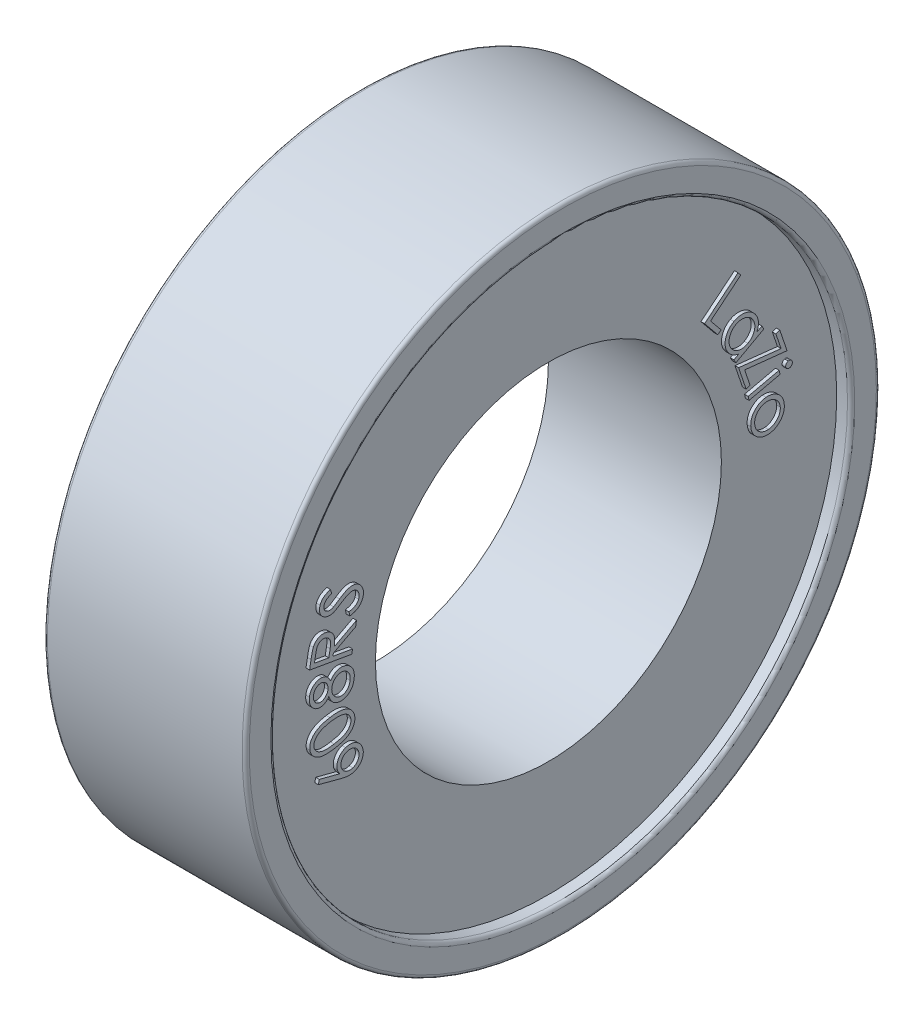
SolidWorks part; units mm, degrees
ref_plane "Front Plane" through (0, 0, 0) normal (0, 0, 1) x (1, 0, 0)
ref_plane "Top Plane" through (0, 0, 0) normal (0, 1, 0) x (1, 0, 0)
ref_plane "Right Plane" through (0, 0, 0) normal (1, 0, 0) x (0, 0, -1)
sketch "Sketch1" plane through (0, 0, 0) normal (1, 0, 0) x (0, 0, -1)
  circle A0 centre (0, 0) radius 6
  circle A1 centre (0, 0) radius 10
  circle A2 centre (0, 0) radius 11
  dimension "D1" = 12
  dimension "D2" = 20
  dimension "D3" = 22
extrude "Boss-Extrude1" add sketch "Sketch1" along normal mid plane 6 contours A1 A0 region at (0, 0, 9.7172)
extrude "Boss-Extrude2" add sketch "Sketch1<3>" along normal mid plane 7 separate body contours A2 A1 region at (0, 0, 10.6889)
sketch "Sketch1<3>" plane through (0, 0, 0) normal (1, 0, 0) x (0, 0, -1) same geometry as "Sketch1"
fillet "Fillet1" radius 0.125 4 edges at (-3.5, 0, -10) (3.5, 0, -10) (3.5, 0, -11) (-3.5, 0, -11)
sketch "Sketch2" plane through (3, 0, 0) normal (1, 0, 0) x (0, 0, -1)
  line L0 (7.8762, 1.8801) -> (7.908, 1.741)
  line L1 (7.908, 1.741) -> (6.8353, 1.4955)
  line L2 (6.8353, 1.4955) -> (6.8035, 1.6347)
  line L3 (6.8035, 1.6347) -> (7.8762, 1.8801)
  line L4 (7.7652, 3.0275) -> (7.9013, 3.0735)
  line L5 (7.9013, 3.0735) -> (8.1528, 2.3304)
  line L6 (8.1528, 2.3304) -> (6.6813, 2.4887)
  line L7 (6.6813, 2.4887) -> (6.8709, 1.9293)
  line L8 (6.8709, 1.9293) -> (6.7339, 1.883)
  line L9 (6.7339, 1.883) -> (6.471, 2.6597)
  line L10 (6.471, 2.6597) -> (7.9446, 2.4978)
  line L11 (7.9446, 2.4978) -> (7.7652, 3.0275)
  line L12 (7.3481, 3.3854) -> (6.3775, 2.8542)
  line L13 (6.3775, 2.8542) -> (6.3102, 2.9771)
  line L14 (6.3102, 2.9771) -> (6.477, 3.0684)
  line L15 (7.1023, 3.4107) -> (7.2808, 3.5083)
  line L16 (7.2808, 3.5083) -> (7.3481, 3.3854)
  line L17 (6.452, 5.5211) -> (6.5472, 5.4045)
  line L18 (6.5472, 5.4045) -> (5.4991, 4.5463)
  line L19 (5.4991, 4.5463) -> (5.8642, 4.1004)
  line L20 (5.8642, 4.1004) -> (5.7522, 4.0088)
  line L21 (5.7522, 4.0088) -> (5.2918, 4.5713)
  line L22 (5.2918, 4.5713) -> (6.452, 5.5211)
  circle A0 centre (0, 0) radius 7 construction
  spline S0 degree 3 poles (8.0554, 0.7678) (8.0592, 0.7269) (8.0581, 0.666) (8.0455, 0.587) (8.0292, 0.531) (8.0076, 0.4772) (7.9701, 0.4074) (7.9327, 0.3603) (7.9054, 0.3306) knots 0 0 0 0 0.258157 0.381467 0.502764 0.62379 0.746181 1 1 1 1
  spline S1 degree 3 poles (7.9054, 0.3306) (7.88, 0.3039) (7.8391, 0.2669) (7.7785, 0.2263) (7.7313, 0.2006) (7.6816, 0.1798) (7.6116, 0.1579) (7.5566, 0.1486) (7.5193, 0.1458) knots 0 0 0 0 0.252774 0.375817 0.498234 0.620232 0.743845 1 1 1 1
  spline S2 degree 3 poles (7.5193, 0.1458) (7.4817, 0.1427) (7.4255, 0.143) (7.3521, 0.1538) (7.2991, 0.1677) (7.2471, 0.1858) (7.197, 0.2099) (7.1482, 0.2388) (7.1013, 0.2725) (7.0578, 0.3106) (7.0186, 0.3523) (6.9849, 0.3975) (6.9564, 0.4461) (6.9329, 0.4978) (6.9084, 0.5727) (6.8986, 0.6319) (6.8952, 0.6722) knots 0 0 0 0 0.124271 0.184364 0.244341 0.304594 0.36529 0.427462 0.491327 0.555432 0.617801 0.679607 0.740874 0.803228 0.866498 1 1 1 1
  spline S3 degree 3 poles (6.8952, 0.6722) (6.8919, 0.7128) (6.8917, 0.7731) (6.9042, 0.8512) (6.9184, 0.9064) (6.9388, 0.9591) (6.9647, 1.0092) (6.9966, 1.0566) (7.0334, 1.1013) (7.0739, 1.1425) (7.1174, 1.179) (7.1632, 1.2107) (7.2111, 1.2376) (7.2613, 1.2598) (7.332, 1.2823) (7.3874, 1.2918) (7.4249, 1.2948) knots 0 0 0 0 0.134008 0.197427 0.259803 0.321276 0.382915 0.445187 0.509142 0.573022 0.635034 0.695942 0.756018 0.815806 0.876072 1 1 1 1
  spline S4 degree 3 poles (7.4249, 1.2948) (7.462, 1.2982) (7.5175, 1.298) (7.59, 1.2879) (7.6422, 1.2753) (7.6929, 1.2576) (7.759, 1.2276) (7.8056, 1.1981) (7.8348, 1.1755) knots 0 0 0 0 0.255345 0.378927 0.501994 0.62354 0.746617 1 1 1 1
  spline S5 degree 3 poles (7.8348, 1.1755) (7.867, 1.1511) (7.9113, 1.1103) (7.9599, 1.0475) (7.9909, 0.9982) (8.0155, 0.9451) (8.0418, 0.8692) (8.0517, 0.8087) (8.0554, 0.7678) knots 0 0 0 0 0.253736 0.375519 0.496864 0.618289 0.741877 1 1 1 1
  spline S6 degree 3 poles (7.9162, 0.7564) (7.9136, 0.7848) (7.9068, 0.8271) (7.8883, 0.8804) (7.8709, 0.9182) (7.8491, 0.9539) (7.8237, 0.988) (7.7941, 1.0198) (7.7609, 1.0493) (7.7253, 1.0761) (7.6878, 1.0992) (7.6488, 1.1179) (7.6085, 1.1327) (7.5667, 1.1433) (7.5085, 1.1516) (7.4639, 1.1521) (7.434, 1.1494) knots 0 0 0 0 0.124131 0.18431 0.24418 0.304608 0.365433 0.428152 0.492772 0.557942 0.621129 0.683312 0.7453 0.807155 0.869949 1 1 1 1
  spline S7 degree 3 poles (7.434, 1.1494) (7.3951, 1.1461) (7.3373, 1.1347) (7.2654, 1.1041) (7.215, 1.0745) (7.1689, 1.0393) (7.1285, 0.999) (7.0944, 0.9541) (7.0671, 0.9047) (7.0468, 0.8522) (7.0287, 0.7787) (7.0267, 0.7214) (7.0298, 0.6834) knots 0 0 0 0 0.170442 0.254484 0.340111 0.424929 0.507159 0.588301 0.670297 0.752376 0.833386 1 1 1 1
  spline S8 degree 3 poles (7.0298, 0.6834) (7.0323, 0.6453) (7.0448, 0.5896) (7.0737, 0.5197) (7.1028, 0.4714) (7.1378, 0.4273) (7.1785, 0.3883) (7.2249, 0.355) (7.2762, 0.328) (7.3308, 0.3069) (7.4068, 0.2887) (7.4656, 0.286) (7.5046, 0.2894) knots 0 0 0 0 0.166167 0.247304 0.329275 0.411434 0.49247 0.574874 0.659582 0.745262 0.829372 1 1 1 1
  spline S9 degree 3 poles (7.5046, 0.2894) (7.5345, 0.2919) (7.5786, 0.2991) (7.6345, 0.3177) (7.674, 0.3346) (7.7112, 0.356) (7.7465, 0.381) (7.7799, 0.4099) (7.8107, 0.4423) (7.8384, 0.477) (7.8621, 0.5136) (7.8824, 0.5509) (7.8976, 0.5898) (7.9089, 0.6299) (7.9181, 0.6854) (7.9186, 0.728) (7.9162, 0.7564) knots 0 0 0 0 0.130234 0.192895 0.254976 0.316474 0.378809 0.44258 0.507432 0.572378 0.635173 0.696213 0.756491 0.816061 0.876427 1 1 1 1
  spline S10 degree 3 poles (8.3338, 1.9123) (8.3368, 1.8974) (8.3389, 1.874) (8.3297, 1.8444) (8.3194, 1.8236) (8.3054, 1.8049) (8.2821, 1.7845) (8.2606, 1.7751) (8.2455, 1.772) knots 0 0 0 0 0.249117 0.371431 0.499065 0.625946 0.749601 1 1 1 1
  spline S11 degree 3 poles (8.2455, 1.772) (8.2308, 1.7686) (8.2077, 1.7675) (8.1784, 1.776) (8.1577, 1.7864) (8.139, 1.8004) (8.1186, 1.8236) (8.1092, 1.845) (8.106, 1.86) knots 0 0 0 0 0.247634 0.368743 0.49724 0.62498 0.74947 1 1 1 1
  spline S12 degree 3 poles (8.106, 1.86) (8.1028, 1.8748) (8.1013, 1.8981) (8.1105, 1.9273) (8.1207, 1.9481) (8.1348, 1.9667) (8.1575, 1.9872) (8.1787, 1.9965) (8.1935, 1.9997) knots 0 0 0 0 0.249802 0.371625 0.500395 0.628406 0.751929 1 1 1 1
  spline S13 degree 3 poles (8.1935, 1.9997) (8.2084, 2.0027) (8.232, 2.0049) (8.2616, 1.9957) (8.2825, 1.9854) (8.301, 1.9713) (8.3217, 1.9486) (8.3302, 1.9269) (8.3338, 1.9123) knots 0 0 0 0 0.251616 0.37436 0.502443 0.629771 0.752635 1 1 1 1
  spline S14 degree 3 poles (6.477, 3.0684) (6.4329, 3.0769) (6.3687, 3.0947) (6.29, 3.1321) (6.2363, 3.1649) (6.1876, 3.2036) (6.1286, 3.2637) (6.092, 3.316) (6.0716, 3.3536) knots 0 0 0 0 0.262596 0.387041 0.50879 0.629258 0.750193 1 1 1 1
  spline S15 degree 3 poles (6.0716, 3.3536) (6.0539, 3.387) (6.0305, 3.4385) (6.0118, 3.5107) (6.0038, 3.5649) (6.001, 3.6198) (6.0039, 3.6753) (6.0133, 3.7314) (6.0275, 3.7876) (6.0472, 3.8422) (6.0711, 3.8944) (6.1003, 3.9426) (6.1334, 3.9877) (6.1715, 4.0293) (6.2291, 4.0805) (6.2776, 4.1133) (6.3123, 4.1318) knots 0 0 0 0 0.125435 0.186055 0.246389 0.306461 0.367542 0.429994 0.494311 0.559108 0.621987 0.683838 0.745229 0.807172 0.869853 1 1 1 1
  spline S16 degree 3 poles (6.3123, 4.1318) (6.3462, 4.1503) (6.3989, 4.1734) (6.472, 4.1934) (6.5268, 4.2025) (6.5823, 4.2058) (6.6384, 4.2034) (6.695, 4.195) (6.7515, 4.1817) (6.8066, 4.1631) (6.859, 4.1404) (6.9075, 4.1127) (6.9522, 4.0805) (6.9938, 4.0445) (7.044, 3.9887) (7.0762, 3.942) (7.0942, 3.9083) knots 0 0 0 0 0.128027 0.190038 0.251026 0.312299 0.374185 0.43699 0.501896 0.566754 0.629566 0.691206 0.751719 0.81226 0.873438 1 1 1 1
  spline S17 degree 3 poles (7.0942, 3.9083) (7.1153, 3.8701) (7.1403, 3.81) (7.1579, 3.7263) (7.1632, 3.6638) (7.1599, 3.6008) (7.1452, 3.5144) (7.1215, 3.4516) (7.1023, 3.4107) knots 0 0 0 0 0.252389 0.373834 0.493677 0.614414 0.737948 1 1 1 1
  spline S18 degree 3 poles (6.9791, 3.8325) (6.9606, 3.8663) (6.9269, 3.9137) (6.8701, 3.9655) (6.8228, 3.9982) (6.7718, 4.0248) (6.7174, 4.0439) (6.6603, 4.0556) (6.6013, 4.0601) (6.5422, 4.0569) (6.4651, 4.0441) (6.4106, 4.0222) (6.3766, 4.0038) knots 0 0 0 0 0.16613 0.248055 0.3306 0.413274 0.495229 0.578574 0.663901 0.749523 0.833235 1 1 1 1
  spline S19 degree 3 poles (6.3766, 4.0038) (6.3425, 3.9856) (6.2956, 3.9507) (6.2427, 3.8929) (6.2083, 3.844) (6.1798, 3.7915) (6.1584, 3.7367) (6.1452, 3.68) (6.1395, 3.6224) (6.1412, 3.565) (6.1537, 3.49) (6.1747, 3.4368) (6.1927, 3.4034) knots 0 0 0 0 0.1663 0.25004 0.336779 0.423141 0.506938 0.589889 0.6732 0.755715 0.836712 1 1 1 1
  spline S20 degree 3 poles (6.1927, 3.4034) (6.2113, 3.3699) (6.2452, 3.3227) (6.3023, 3.2703) (6.3501, 3.2363) (6.4016, 3.2084) (6.4557, 3.1879) (6.5114, 3.1755) (6.5685, 3.1711) (6.626, 3.1744) (6.7034, 3.1897) (6.7591, 3.2124) (6.7943, 3.2319) knots 0 0 0 0 0.164964 0.247568 0.332185 0.416782 0.4987 0.579895 0.661556 0.743958 0.826908 1 1 1 1
  spline S21 degree 3 poles (6.7943, 3.2319) (6.8212, 3.2468) (6.8597, 3.2716) (6.9045, 3.3118) (6.9346, 3.3435) (6.9601, 3.3785) (6.9825, 3.4155) (7.0012, 3.4552) (7.0161, 3.4969) (7.0268, 3.5398) (7.0336, 3.5827) (7.0357, 3.6254) (7.0332, 3.6677) (7.0267, 3.7097) (7.0115, 3.766) (6.9933, 3.8064) (6.9791, 3.8325) knots 0 0 0 0 0.131762 0.19487 0.257 0.318258 0.379748 0.441831 0.505512 0.56868 0.630656 0.69113 0.751199 0.811483 0.872685 1 1 1 1
  dimension "D1" = 14
extrude "Boss-Extrude3" add sketch "Sketch2" along normal blind 0.125
sketch "Sketch4" plane through (3, 0, 0) normal (1, 0, 0) x (0, 0, -1)
  line L0 (-7.0116, 1.9412) -> (-7.0414, 2.0861)
  line L1 (-7.6826, 3.0749) -> (-7.6357, 2.9295)
  line L2 (-8.4081, 1.0172) -> (-8.3573, 1.309)
  line L3 (-7.5532, 1.2907) -> (-6.7804, 1.6987)
  line L4 (-6.7804, 1.6987) -> (-6.8119, 1.5175)
  line L5 (-6.8119, 1.5175) -> (-7.5845, 1.1107)
  line L6 (-7.5845, 1.1107) -> (-7.5992, 1.0268)
  line L7 (-7.5992, 1.0268) -> (-6.9183, 0.9081)
  line L8 (-6.9183, 0.9081) -> (-6.9438, 0.7618)
  line L9 (-6.9438, 0.7618) -> (-8.4081, 1.0172)
  line L10 (-8.2392, 1.1386) -> (-7.7413, 1.0518)
  line L11 (-7.7413, 1.0518) -> (-7.6956, 1.3033)
  line L12 (-8.1941, 1.3964) -> (-8.2392, 1.1386)
  line L13 (-8.1056, -2.5772) -> (-8.0695, -2.435)
  line L14 (-8.0695, -2.435) -> (-7.3625, -2.618)
  line L15 (-7.3213, -2.786) -> (-8.1056, -2.5772)
  circle A0 centre (0, 0) radius 7 construction
  circle A1 centre (0, 0) radius 7 construction
  spline S0 degree 3 poles (-7.0414, 2.0861) (-6.9992, 2.093) (-6.939, 2.1066) (-6.8655, 2.1349) (-6.8199, 2.1595) (-6.7808, 2.1879) (-6.7382, 2.2304) (-6.7163, 2.2693) (-6.7067, 2.2967) knots 0 0 0 0 0.30903 0.443489 0.567782 0.682656 0.79058 1 1 1 1
  spline S1 degree 3 poles (-6.7067, 2.2967) (-6.6987, 2.3198) (-6.6901, 2.3558) (-6.6892, 2.4047) (-6.6924, 2.4411) (-6.6998, 2.4765) (-6.7114, 2.5098) (-6.7275, 2.5403) (-6.7478, 2.5674) (-6.7708, 2.5918) (-6.8051, 2.6192) (-6.8343, 2.6342) (-6.8548, 2.641) knots 0 0 0 0 0.176041 0.26327 0.35155 0.438479 0.522589 0.604154 0.685594 0.766137 0.844585 1 1 1 1
  spline S2 degree 3 poles (-6.8548, 2.641) (-6.8786, 2.6493) (-6.9314, 2.6582) (-6.984, 2.649) (-7.0104, 2.6416) knots 0 0 0 0 0.477935 1 1 1 1
  spline S3 degree 3 poles (-7.0104, 2.6416) (-7.0321, 2.6359) (-7.0649, 2.623) (-7.1102, 2.6034) (-7.1476, 2.5842) (-7.1877, 2.5626) (-7.2463, 2.5284) (-7.2904, 2.4996) (-7.3208, 2.4797) knots 0 0 0 0 0.190823 0.301106 0.420821 0.550165 0.689663 1 1 1 1
  spline S4 degree 3 poles (-7.3208, 2.4797) (-7.3506, 2.4601) (-7.3933, 2.4322) (-7.4486, 2.3983) (-7.4843, 2.3777) (-7.516, 2.36) (-7.5506, 2.343) (-7.5749, 2.3322) (-7.5904, 2.3276) knots 0 0 0 0 0.344759 0.493456 0.626712 0.743765 0.844275 1 1 1 1
  spline S5 degree 3 poles (-7.5904, 2.3276) (-7.6107, 2.321) (-7.6415, 2.3139) (-7.683, 2.3089) (-7.7135, 2.3077) (-7.7436, 2.3088) (-7.7835, 2.3142) (-7.8129, 2.3216) (-7.832, 2.3285) knots 0 0 0 0 0.260143 0.385642 0.509156 0.631449 0.753461 1 1 1 1
  spline S6 degree 3 poles (-7.832, 2.3285) (-7.8613, 2.3394) (-7.9041, 2.3593) (-7.9528, 2.3979) (-7.9851, 2.4306) (-8.0124, 2.4675) (-8.0343, 2.5077) (-8.0507, 2.551) (-8.061, 2.5969) (-8.0658, 2.6442) (-8.0643, 2.7083) (-8.0532, 2.7555) (-8.0429, 2.7859) knots 0 0 0 0 0.167519 0.249059 0.330764 0.412608 0.493039 0.574805 0.658762 0.743712 0.828256 1 1 1 1
  spline S7 degree 3 poles (-8.0429, 2.7859) (-8.0313, 2.8183) (-8.0085, 2.8651) (-7.9656, 2.9193) (-7.9348, 2.9502) (-7.9065, 2.9728) (-7.8824, 2.9894) (-7.8555, 3.0048) (-7.8263, 3.0203) (-7.7942, 3.0348) (-7.7465, 3.0544) (-7.7087, 3.0668) (-7.6826, 3.0749) knots 0 0 0 0 0.214698 0.320898 0.428973 0.485773 0.546336 0.610639 0.679005 0.752422 0.829923 1 1 1 1
  spline S8 degree 3 poles (-7.6357, 2.9295) (-7.6562, 2.9225) (-7.686, 2.9128) (-7.7234, 2.8978) (-7.748, 2.887) (-7.7702, 2.8763) (-7.7896, 2.865) (-7.807, 2.8545) (-7.826, 2.8396) (-7.8468, 2.8198) (-7.8754, 2.7846) (-7.8903, 2.7537) (-7.8981, 2.7324) knots 0 0 0 0 0.189767 0.274924 0.353598 0.425104 0.490811 0.550037 0.60328 0.702703 0.800802 1 1 1 1
  spline S9 degree 3 poles (-7.8981, 2.7324) (-7.9069, 2.7061) (-7.9155, 2.6652) (-7.9086, 2.6113) (-7.8963, 2.5744) (-7.8774, 2.5411) (-7.8438, 2.5032) (-7.8103, 2.4845) (-7.7866, 2.4761) knots 0 0 0 0 0.267612 0.392727 0.517519 0.639529 0.758148 1 1 1 1
  spline S10 degree 3 poles (-7.7866, 2.4761) (-7.7715, 2.4705) (-7.7478, 2.4652) (-7.7155, 2.4627) (-7.6904, 2.4637) (-7.6638, 2.4676) (-7.6236, 2.4786) (-7.5932, 2.4908) (-7.5726, 2.501) knots 0 0 0 0 0.217706 0.326461 0.437698 0.556948 0.690119 1 1 1 1
  spline S11 degree 3 poles (-7.5726, 2.501) (-7.5635, 2.5055) (-7.5484, 2.5151) (-7.5252, 2.5291) (-7.5018, 2.5443) (-7.474, 2.5623) (-7.4291, 2.5927) (-7.3932, 2.6167) (-7.368, 2.6338) knots 0 0 0 0 0.125281 0.21926 0.333345 0.468593 0.625691 1 1 1 1
  spline S12 degree 3 poles (-7.368, 2.6338) (-7.3367, 2.6549) (-7.2909, 2.685) (-7.2296, 2.7204) (-7.1875, 2.7428) (-7.1477, 2.7624) (-7.1098, 2.7782) (-7.0744, 2.7915) (-7.0407, 2.8008) (-7.0084, 2.8074) (-6.9771, 2.8124) (-6.9465, 2.8147) (-6.9166, 2.8151) (-6.8874, 2.8133) (-6.8496, 2.8082) (-6.8222, 2.8004) (-6.8043, 2.7946) knots 0 0 0 0 0.186084 0.2699 0.34873 0.421139 0.48861 0.550601 0.607487 0.660923 0.712861 0.763363 0.812231 0.860202 0.907041 1 1 1 1
  spline S13 degree 3 poles (-6.8043, 2.7946) (-6.7794, 2.786) (-6.7438, 2.7692) (-6.7003, 2.7405) (-6.6706, 2.7157) (-6.6438, 2.6875) (-6.6193, 2.6564) (-6.5974, 2.6221) (-6.5784, 2.585) (-6.5625, 2.5463) (-6.5505, 2.5066) (-6.5421, 2.4666) (-6.5387, 2.4262) (-6.5389, 2.3854) (-6.5446, 2.33) (-6.5553, 2.289) (-6.5648, 2.2621) knots 0 0 0 0 0.121894 0.181422 0.240656 0.300328 0.361071 0.423823 0.48851 0.553589 0.617527 0.679984 0.74235 0.804933 0.86831 1 1 1 1
  spline S14 degree 3 poles (-6.5648, 2.2621) (-6.5728, 2.2414) (-6.5847, 2.2104) (-6.6069, 2.1726) (-6.6246, 2.1455) (-6.6444, 2.1202) (-6.6659, 2.0961) (-6.6896, 2.0738) (-6.715, 2.0527) (-6.743, 2.0335) (-6.7732, 2.0154) (-6.8063, 1.9991) (-6.8421, 1.9845) (-6.8806, 1.9713) (-6.937, 1.9553) (-6.9813, 1.9463) (-7.0116, 1.9412) knots 0 0 0 0 0.114729 0.170788 0.226006 0.281656 0.336582 0.392913 0.449127 0.507081 0.567831 0.630734 0.697284 0.767277 0.840936 1 1 1 1
  spline S15 degree 3 poles (-8.3573, 1.309) (-8.3506, 1.3464) (-8.3412, 1.4001) (-8.3268, 1.4678) (-8.3169, 1.5112) (-8.3074, 1.5496) (-8.2959, 1.591) (-8.2866, 1.6194) (-8.2795, 1.6362) knots 0 0 0 0 0.338375 0.485158 0.61694 0.734633 0.837436 1 1 1 1
  spline S16 degree 3 poles (-8.2795, 1.6362) (-8.2711, 1.6565) (-8.2559, 1.6855) (-8.2322, 1.7217) (-8.2123, 1.7463) (-8.1907, 1.7691) (-8.1674, 1.7901) (-8.1419, 1.8091) (-8.115, 1.8263) (-8.0865, 1.8409) (-8.057, 1.8531) (-8.0262, 1.862) (-7.9945, 1.8684) (-7.962, 1.872) (-7.9165, 1.8727) (-7.8821, 1.8691) (-7.8591, 1.8652) knots 0 0 0 0 0.126764 0.188483 0.249325 0.30902 0.369597 0.430288 0.491864 0.553649 0.61483 0.676284 0.738176 0.800985 0.865154 1 1 1 1
  spline S17 degree 3 poles (-7.8591, 1.8652) (-7.8212, 1.8588) (-7.7664, 1.8426) (-7.701, 1.8062) (-7.6579, 1.7734) (-7.6203, 1.7349) (-7.5897, 1.6906) (-7.5654, 1.6415) (-7.5514, 1.5966) (-7.5434, 1.5581) (-7.5393, 1.5264) (-7.537, 1.4925) (-7.5363, 1.4564) (-7.5381, 1.4181) (-7.5419, 1.3624) (-7.5485, 1.3198) (-7.5532, 1.2907) knots 0 0 0 0 0.155737 0.229158 0.302154 0.374503 0.446242 0.519591 0.595855 0.636062 0.679066 0.725056 0.773779 0.825377 0.880333 1 1 1 1
  spline S18 degree 3 poles (-7.6956, 1.3033) (-7.6918, 1.3261) (-7.6863, 1.3593) (-7.6824, 1.4023) (-7.6801, 1.431) (-7.6794, 1.4576) (-7.6805, 1.4819) (-7.682, 1.504) (-7.6865, 1.5302) (-7.6948, 1.5604) (-7.7101, 1.5936) (-7.73, 1.6238) (-7.7553, 1.65) (-7.7836, 1.673) (-7.8262, 1.6973) (-7.8615, 1.7087) (-7.8858, 1.7128) knots 0 0 0 0 0.135147 0.195553 0.251738 0.303119 0.350432 0.393187 0.432244 0.505047 0.575047 0.644499 0.71511 0.786124 0.856209 1 1 1 1
  spline S19 degree 3 poles (-7.8858, 1.7128) (-7.9095, 1.7171) (-7.9458, 1.7186) (-7.9929, 1.7091) (-8.0267, 1.6971) (-8.0582, 1.6807) (-8.0864, 1.6601) (-8.1112, 1.6358) (-8.1285, 1.6119) (-8.1402, 1.5899) (-8.1493, 1.5707) (-8.1576, 1.5486) (-8.1657, 1.5236) (-8.1735, 1.4958) (-8.1833, 1.4532) (-8.1905, 1.4198) (-8.1941, 1.3964) knots 0 0 0 0 0.142972 0.213479 0.284947 0.355618 0.424306 0.492182 0.561353 0.598705 0.640847 0.687462 0.7395 0.797073 0.858967 1 1 1 1
  spline S20 degree 3 poles (-7.6815, 0.3232) (-7.6667, 0.3455) (-7.6432, 0.3768) (-7.6101, 0.4156) (-7.5854, 0.4409) (-7.5604, 0.4635) (-7.5352, 0.4834) (-7.5096, 0.5007) (-7.4753, 0.5198) (-7.4306, 0.5379) (-7.3552, 0.556) (-7.2963, 0.5561) (-7.2575, 0.5507) knots 0 0 0 0 0.156963 0.229995 0.299086 0.364926 0.4278 0.488036 0.546002 0.658467 0.769817 1 1 1 1
  spline S21 degree 3 poles (-7.2575, 0.5507) (-7.2299, 0.5465) (-7.1888, 0.5385) (-7.1372, 0.5189) (-7.1001, 0.5022) (-7.0651, 0.481) (-7.0201, 0.4487) (-6.9894, 0.4201) (-6.9709, 0.3989) knots 0 0 0 0 0.253618 0.376397 0.499309 0.621682 0.745737 1 1 1 1
  spline S22 degree 3 poles (-6.9709, 0.3989) (-6.9473, 0.3733) (-6.9176, 0.3303) (-6.8883, 0.2671) (-6.8722, 0.2167) (-6.8612, 0.1633) (-6.8546, 0.0862) (-6.858, 0.0268) (-6.8633, -0.0133) knots 0 0 0 0 0.23658 0.353837 0.47362 0.596221 0.724369 1 1 1 1
  spline S23 degree 3 poles (-6.8633, -0.0133) (-6.8687, -0.0517) (-6.8795, -0.1078) (-6.9043, -0.1774) (-6.9257, -0.2242) (-6.952, -0.2661) (-6.9813, -0.3045) (-7.0153, -0.3379) (-7.0526, -0.3669) (-7.0917, -0.3915) (-7.1316, -0.4125) (-7.1719, -0.4294) (-7.2126, -0.4421) (-7.2537, -0.4505) (-7.3092, -0.4566) (-7.3512, -0.4553) (-7.3789, -0.4514) knots 0 0 0 0 0.153701 0.224809 0.292216 0.357027 0.420319 0.482844 0.545267 0.606758 0.665817 0.723402 0.779462 0.834518 0.889165 1 1 1 1
  spline S24 degree 3 poles (-7.3789, -0.4514) (-7.3991, -0.4488) (-7.4288, -0.4426) (-7.4669, -0.4305) (-7.4942, -0.4196) (-7.5204, -0.4066) (-7.5456, -0.3916) (-7.5698, -0.3747) (-7.5931, -0.3558) (-7.615, -0.3342) (-7.6363, -0.3104) (-7.6559, -0.2835) (-7.6749, -0.2543) (-7.693, -0.2224) (-7.716, -0.175) (-7.7304, -0.1371) (-7.7395, -0.111) knots 0 0 0 0 0.116139 0.172503 0.227873 0.283308 0.339148 0.39493 0.45176 0.50993 0.570223 0.633515 0.699585 0.769162 0.842227 1 1 1 1
  spline S25 degree 3 poles (-7.7395, -0.111) (-7.7616, -0.1423) (-7.798, -0.1855) (-7.8557, -0.2306) (-7.9, -0.256) (-7.9458, -0.2742) (-8.0078, -0.2893) (-8.0557, -0.2894) (-8.0869, -0.2855) knots 0 0 0 0 0.28116 0.410277 0.534465 0.653649 0.769824 1 1 1 1
  spline S26 degree 3 poles (-8.0869, -0.2855) (-8.1193, -0.2817) (-8.1669, -0.2666) (-8.2262, -0.2347) (-8.2687, -0.2032) (-8.308, -0.1661) (-8.3415, -0.123) (-8.3702, -0.0757) (-8.392, -0.0235) (-8.4084, 0.0312) (-8.4203, 0.1075) (-8.4194, 0.1657) (-8.4141, 0.2042) knots 0 0 0 0 0.149699 0.227184 0.308892 0.392287 0.474935 0.559213 0.645874 0.734192 0.821419 1 1 1 1
  spline S27 degree 3 poles (-8.4141, 0.2042) (-8.409, 0.2416) (-8.3956, 0.2967) (-8.3633, 0.3644) (-8.3337, 0.4115) (-8.2987, 0.4541) (-8.259, 0.491) (-8.2155, 0.5225) (-8.168, 0.5467) (-8.1187, 0.5652) (-8.052, 0.5802) (-8.001, 0.5805) (-7.9679, 0.5762) knots 0 0 0 0 0.175505 0.261648 0.348195 0.433988 0.517459 0.600014 0.683018 0.765046 0.844349 1 1 1 1
  spline S28 degree 3 poles (-7.9679, 0.5762) (-7.936, 0.5716) (-7.8888, 0.5598) (-7.8331, 0.5287) (-7.7952, 0.4999) (-7.7609, 0.4648) (-7.7184, 0.408) (-7.6952, 0.3581) (-7.6815, 0.3232) knots 0 0 0 0 0.240515 0.356344 0.473437 0.59368 0.720466 1 1 1 1
  spline S29 degree 3 poles (-8.2716, 0.1778) (-8.2738, 0.1584) (-8.2763, 0.1294) (-8.2732, 0.0915) (-8.2691, 0.0644) (-8.2623, 0.0384) (-8.2526, 0.0135) (-8.2415, -0.0107) (-8.2272, -0.0333) (-8.2116, -0.0545) (-8.1942, -0.0732) (-8.176, -0.0899) (-8.1562, -0.1037) (-8.1355, -0.1155) (-8.106, -0.1283) (-8.0823, -0.1337) (-8.0661, -0.1359) knots 0 0 0 0 0.140664 0.207791 0.272638 0.337409 0.400507 0.464254 0.528572 0.592344 0.652962 0.71208 0.769395 0.826443 0.882866 1 1 1 1
  spline S30 degree 3 poles (-8.0661, -0.1359) (-8.0499, -0.1377) (-8.0253, -0.1389) (-7.9929, -0.134) (-7.969, -0.1271) (-7.9452, -0.1182) (-7.9216, -0.1064) (-7.8985, -0.0915) (-7.8759, -0.0742) (-7.8545, -0.055) (-7.8351, -0.0342) (-7.8183, -0.0121) (-7.8033, 0.011) (-7.7915, 0.0356) (-7.7778, 0.0699) (-7.7724, 0.0975) (-7.7695, 0.1159) knots 0 0 0 0 0.114368 0.171043 0.228496 0.2877 0.348797 0.412739 0.479719 0.547677 0.613611 0.67807 0.742012 0.805303 0.869184 1 1 1 1
  spline S31 degree 3 poles (-7.7695, 0.1159) (-7.7664, 0.1399) (-7.7663, 0.1765) (-7.7751, 0.2245) (-7.7866, 0.2595) (-7.802, 0.2929) (-7.8214, 0.3238) (-7.845, 0.3512) (-7.872, 0.375) (-7.901, 0.395) (-7.9404, 0.4164) (-7.9725, 0.4249) (-7.9937, 0.4281) knots 0 0 0 0 0.170726 0.256289 0.343266 0.430572 0.515113 0.599854 0.684992 0.768344 0.848364 1 1 1 1
  spline S32 degree 3 poles (-7.9937, 0.4281) (-8.0233, 0.4327) (-8.0693, 0.4282) (-8.1274, 0.4052) (-8.1624, 0.3831) (-8.1887, 0.3611) (-8.2074, 0.3422) (-8.2232, 0.3203) (-8.2371, 0.2963) (-8.2491, 0.2701) (-8.2627, 0.2308) (-8.2685, 0.1993) (-8.2716, 0.1778) knots 0 0 0 0 0.213393 0.325501 0.446089 0.508922 0.572022 0.636353 0.702133 0.771035 0.8434 1 1 1 1
  spline S33 degree 3 poles (-7.6355, 0.1003) (-7.6393, 0.0757) (-7.6406, 0.039) (-7.6369, -0.0093) (-7.63, -0.0436) (-7.6205, -0.0769) (-7.6075, -0.1091) (-7.5908, -0.1399) (-7.5714, -0.1695) (-7.5498, -0.197) (-7.5257, -0.2213) (-7.5011, -0.2433) (-7.4742, -0.2612) (-7.4465, -0.2769) (-7.4067, -0.2928) (-7.3754, -0.3005) (-7.354, -0.3033) knots 0 0 0 0 0.136072 0.20116 0.264973 0.327938 0.390809 0.454985 0.520077 0.584627 0.646814 0.707205 0.765744 0.823559 0.881736 1 1 1 1
  spline S34 degree 3 poles (-7.354, -0.3033) (-7.3273, -0.307) (-7.2864, -0.3069) (-7.2331, -0.295) (-7.1939, -0.2807) (-7.1567, -0.2609) (-7.1225, -0.2362) (-7.0921, -0.2062) (-7.0654, -0.1715) (-7.0425, -0.1324) (-7.0179, -0.0734) (-7.0067, -0.0257) (-7.0027, 0.0074) knots 0 0 0 0 0.153886 0.231293 0.311202 0.391658 0.471625 0.551819 0.635107 0.721356 0.80965 1 1 1 1
  spline S35 degree 3 poles (-7.0027, 0.0074) (-6.9989, 0.0331) (-6.9971, 0.0711) (-7.0006, 0.1208) (-7.0065, 0.1556) (-7.016, 0.1886) (-7.0282, 0.2201) (-7.0444, 0.2497) (-7.0632, 0.2775) (-7.0844, 0.3031) (-7.1073, 0.326) (-7.1315, 0.3461) (-7.1572, 0.3633) (-7.1843, 0.3779) (-7.2228, 0.3932) (-7.2534, 0.4) (-7.2741, 0.4029) knots 0 0 0 0 0.145018 0.212489 0.278488 0.342027 0.404706 0.467174 0.530156 0.592685 0.652948 0.711097 0.768479 0.825669 0.883038 1 1 1 1
  spline S36 degree 3 poles (-7.2741, 0.4029) (-7.2942, 0.4052) (-7.3248, 0.4069) (-7.3649, 0.4009) (-7.3945, 0.3937) (-7.4235, 0.3827) (-7.4522, 0.3689) (-7.4803, 0.3515) (-7.5076, 0.3314) (-7.5333, 0.3087) (-7.5565, 0.284) (-7.577, 0.2576) (-7.5947, 0.2294) (-7.6089, 0.1995) (-7.6255, 0.1571) (-7.6326, 0.1233) (-7.6355, 0.1003) knots 0 0 0 0 0.117061 0.174623 0.232151 0.291716 0.352483 0.41528 0.481143 0.547217 0.611975 0.676001 0.739101 0.802442 0.866592 1 1 1 1
  spline S37 degree 3 poles (-7.5368, -1.769) (-7.5828, -1.7767) (-7.6501, -1.7861) (-7.7376, -1.7937) (-7.7973, -1.7964) (-7.8533, -1.7969) (-7.9054, -1.7946) (-7.9538, -1.7895) (-7.9986, -1.7817) (-8.0403, -1.7713) (-8.0798, -1.7595) (-8.117, -1.7452) (-8.152, -1.7291) (-8.185, -1.711) (-8.2158, -1.6908) (-8.2444, -1.6685) (-8.2708, -1.6442) (-8.2949, -1.6183) (-8.3165, -1.5909) (-8.3359, -1.5623) (-8.3527, -1.5325) (-8.3672, -1.5014) (-8.3835, -1.4581) (-8.3912, -1.4239) (-8.3953, -1.4009) knots 0 0 0 0 0.133063 0.193903 0.250579 0.303766 0.353574 0.399583 0.442552 0.483193 0.522359 0.560011 0.596859 0.632437 0.667333 0.701767 0.735968 0.769554 0.802735 0.83549 0.868014 0.900508 0.933173 1 1 1 1
  spline S38 degree 3 poles (-8.3953, -1.4009) (-8.3991, -1.3775) (-8.4024, -1.3422) (-8.4012, -1.2952) (-8.3976, -1.2606) (-8.3912, -1.2265) (-8.3822, -1.1928) (-8.3704, -1.1596) (-8.356, -1.1267) (-8.3386, -1.0947) (-8.3184, -1.0637) (-8.2954, -1.0337) (-8.2695, -1.0048) (-8.2406, -0.9772) (-8.2088, -0.9508) (-8.1745, -0.9251) (-8.1371, -0.9008) (-8.0965, -0.8774) (-8.0517, -0.8563) (-8.0033, -0.836) (-7.9507, -0.818) (-7.8946, -0.801) (-7.8122, -0.7802) (-7.7478, -0.7676) (-7.7036, -0.7603) knots 0 0 0 0 0.067327 0.100279 0.133112 0.16575 0.198675 0.231817 0.265638 0.300199 0.335091 0.370533 0.407132 0.444891 0.483794 0.524174 0.566233 0.610366 0.656979 0.706499 0.759126 0.814285 0.872896 1 1 1 1
  spline S39 degree 3 poles (-7.7036, -0.7603) (-7.6595, -0.753) (-7.5948, -0.744) (-7.5104, -0.7375) (-7.4519, -0.7348) (-7.3967, -0.7354) (-7.3446, -0.7388) (-7.2958, -0.7442) (-7.2502, -0.7532) (-7.2072, -0.7639) (-7.1667, -0.7769) (-7.1281, -0.7915) (-7.0919, -0.8084) (-7.0581, -0.8274) (-7.0266, -0.8484) (-6.9972, -0.8713) (-6.9703, -0.8963) (-6.9455, -0.9227) (-6.9233, -0.9506) (-6.9037, -0.9798) (-6.8861, -1.0099) (-6.8719, -1.0418) (-6.8549, -1.0858) (-6.8472, -1.1206) (-6.843, -1.144) knots 0 0 0 0 0.126726 0.185153 0.240324 0.292611 0.341867 0.388215 0.431905 0.47353 0.513789 0.552734 0.590362 0.626876 0.662733 0.697748 0.732536 0.766714 0.800485 0.833428 0.866522 0.899327 0.932418 1 1 1 1
  spline S40 degree 3 poles (-6.843, -1.144) (-6.8392, -1.1671) (-6.8359, -1.2018) (-6.8372, -1.248) (-6.8407, -1.2819) (-6.8472, -1.3154) (-6.8558, -1.3484) (-6.8677, -1.3809) (-6.882, -1.413) (-6.8992, -1.4442) (-6.9187, -1.4745) (-6.9415, -1.5033) (-6.9666, -1.5314) (-6.9952, -1.5577) (-7.0259, -1.5835) (-7.0595, -1.608) (-7.0962, -1.6313) (-7.1364, -1.6534) (-7.1807, -1.6741) (-7.2293, -1.6932) (-7.2822, -1.7113) (-7.3397, -1.7277) (-7.4247, -1.7486) (-7.4911, -1.7616) (-7.5368, -1.769) knots 0 0 0 0 0.06671 0.099345 0.131864 0.164193 0.196471 0.22933 0.262891 0.296829 0.33096 0.365823 0.401686 0.438534 0.47653 0.516253 0.557297 0.600714 0.647184 0.696765 0.749977 0.806857 0.867588 1 1 1 1
  spline S41 degree 3 poles (-7.557, -1.6287) (-7.5178, -1.622) (-7.461, -1.6118) (-7.3886, -1.5946) (-7.3402, -1.5819) (-7.2957, -1.5682) (-7.2553, -1.5534) (-7.219, -1.5382) (-7.1863, -1.5222) (-7.157, -1.5047) (-7.1298, -1.4869) (-7.105, -1.4677) (-7.0822, -1.4478) (-7.0617, -1.4266) (-7.0431, -1.4047) (-7.0273, -1.3813) (-7.0086, -1.3498) (-6.9909, -1.3092) (-6.9729, -1.2438) (-6.972, -1.1934) (-6.9776, -1.1611) knots 0 0 0 0 0.143347 0.207897 0.26807 0.324033 0.375553 0.422967 0.466083 0.506709 0.545766 0.583105 0.61969 0.654929 0.68928 0.723033 0.756537 0.821211 0.882175 1 1 1 1
  spline S42 degree 3 poles (-6.9776, -1.1611) (-6.9829, -1.1288) (-6.9991, -1.0811) (-7.0369, -1.0255) (-7.0663, -0.9933) (-7.0934, -0.9697) (-7.1158, -0.9532) (-7.1404, -0.939) (-7.1663, -0.9255) (-7.1946, -0.9147) (-7.235, -0.901) (-7.2671, -0.8942) (-7.2889, -0.8907) knots 0 0 0 0 0.222467 0.336275 0.455245 0.517469 0.579808 0.643879 0.710224 0.778335 0.849348 1 1 1 1
  spline S43 degree 3 poles (-7.2889, -0.8907) (-7.3177, -0.8857) (-7.3619, -0.8804) (-7.4223, -0.8777) (-7.4701, -0.8779) (-7.5197, -0.8795) (-7.5892, -0.8856) (-7.6421, -0.8922) (-7.6778, -0.8982) knots 0 0 0 0 0.223977 0.341776 0.464067 0.591056 0.72225 1 1 1 1
  spline S44 degree 3 poles (-7.6778, -0.8982) (-7.7132, -0.9043) (-7.765, -0.9142) (-7.8318, -0.9304) (-7.8778, -0.9438) (-7.9211, -0.9577) (-7.9616, -0.9731) (-7.9994, -0.9895) (-8.0343, -1.0073) (-8.0665, -1.026) (-8.0964, -1.0451) (-8.1235, -1.0652) (-8.1479, -1.0864) (-8.17, -1.1079) (-8.1893, -1.1307) (-8.2062, -1.154) (-8.2247, -1.1857) (-8.2423, -1.226) (-8.2605, -1.2907) (-8.2606, -1.3407) (-8.2556, -1.3727) knots 0 0 0 0 0.129652 0.190312 0.24785 0.302596 0.354415 0.404103 0.451139 0.495834 0.53844 0.578991 0.617683 0.654741 0.690375 0.725079 0.758613 0.822539 0.88321 1 1 1 1
  spline S45 degree 3 poles (-8.2556, -1.3727) (-8.2505, -1.4052) (-8.2336, -1.4528) (-8.196, -1.5091) (-8.1661, -1.5414) (-8.1385, -1.565) (-8.116, -1.5817) (-8.0914, -1.5964) (-8.0652, -1.6096) (-8.0373, -1.6213) (-8.0077, -1.6312) (-7.9764, -1.6396) (-7.943, -1.6466) (-7.9069, -1.6519) (-7.8675, -1.6542) (-7.8246, -1.6552) (-7.7781, -1.6538) (-7.7279, -1.651) (-7.6536, -1.6431) (-7.5963, -1.6354) (-7.557, -1.6287) knots 0 0 0 0 0.118558 0.179266 0.243168 0.276468 0.310061 0.344255 0.379469 0.415894 0.453244 0.492146 0.532737 0.576156 0.623584 0.674885 0.730889 0.791316 0.856297 1 1 1 1
  spline S46 degree 3 poles (-7.3625, -2.618) (-7.3795, -2.5969) (-7.4073, -2.5533) (-7.4301, -2.5069) (-7.4376, -2.4834) knots 0 0 0 0 0.524253 1 1 1 1
  spline S47 degree 3 poles (-7.4376, -2.4834) (-7.4469, -2.4564) (-7.4574, -2.4151) (-7.4616, -2.3592) (-7.4612, -2.3181) (-7.456, -2.2772) (-7.4463, -2.2366) (-7.4323, -2.1964) (-7.4144, -2.1569) (-7.3927, -2.1193) (-7.3679, -2.0839) (-7.34, -2.0519) (-7.3091, -2.0226) (-7.2749, -1.9969) (-7.2251, -1.9656) (-7.1837, -1.9486) (-7.1555, -1.9383) knots 0 0 0 0 0.125365 0.185749 0.245506 0.305285 0.36624 0.428068 0.491771 0.556128 0.61854 0.680824 0.742363 0.804751 0.8679 1 1 1 1
  spline S48 degree 3 poles (-7.1555, -1.9383) (-7.1166, -1.925) (-7.0564, -1.9117) (-6.9754, -1.9108) (-6.9163, -1.9184) (-6.8589, -1.9336) (-6.8041, -1.9568) (-6.7525, -1.9877) (-6.7047, -2.026) (-6.6612, -2.0697) (-6.6114, -2.1355) (-6.5837, -2.1912) (-6.5707, -2.2304) knots 0 0 0 0 0.169399 0.251067 0.332561 0.414098 0.494684 0.576806 0.661059 0.74622 0.830113 1 1 1 1
  spline S49 degree 3 poles (-6.5707, -2.2304) (-6.558, -2.2681) (-6.545, -2.3266) (-6.5449, -2.406) (-6.552, -2.4649) (-6.5666, -2.5223) (-6.5889, -2.577) (-6.6196, -2.6279) (-6.6566, -2.6752) (-6.6998, -2.7173) (-6.7635, -2.7659) (-6.8177, -2.7924) (-6.8556, -2.8049) knots 0 0 0 0 0.167098 0.249144 0.332644 0.41561 0.497494 0.579754 0.664261 0.749057 0.832535 1 1 1 1
  spline S50 degree 3 poles (-6.8556, -2.8049) (-6.8852, -2.8153) (-6.9322, -2.8259) (-6.9975, -2.8321) (-7.0409, -2.8328) (-7.0774, -2.8313) (-7.1069, -2.8283) (-7.1384, -2.8251) (-7.1714, -2.8192) (-7.2064, -2.8132) (-7.2566, -2.8022) (-7.2951, -2.793) (-7.3213, -2.786) knots 0 0 0 0 0.198656 0.304571 0.415096 0.47358 0.536082 0.603202 0.673993 0.748862 0.828085 1 1 1 1
  spline S51 degree 3 poles (-7.3027, -2.4744) (-7.2958, -2.4941) (-7.2835, -2.5228) (-7.2611, -2.5572) (-7.2423, -2.5807) (-7.2217, -2.6027) (-7.1979, -2.6217) (-7.1723, -2.6394) (-7.1446, -2.6545) (-7.1156, -2.6671) (-7.086, -2.6767) (-7.0563, -2.6835) (-7.0262, -2.6867) (-6.996, -2.687) (-6.9549, -2.6834) (-6.9245, -2.6756) (-6.9045, -2.6688) knots 0 0 0 0 0.12703 0.188751 0.249494 0.31029 0.371799 0.434532 0.499194 0.563634 0.626482 0.688308 0.749033 0.81 0.871817 1 1 1 1
  spline S52 degree 3 poles (-6.9045, -2.6688) (-6.8849, -2.6619) (-6.8562, -2.6497) (-6.8217, -2.6271) (-6.7979, -2.6086) (-6.7763, -2.5877) (-6.7572, -2.564) (-6.7396, -2.5384) (-6.7245, -2.5107) (-6.7119, -2.4817) (-6.7022, -2.4522) (-6.6955, -2.4226) (-6.6918, -2.3927) (-6.6915, -2.3625) (-6.6959, -2.3217) (-6.7027, -2.2913) (-6.7098, -2.2716) knots 0 0 0 0 0.127252 0.189081 0.25041 0.310873 0.37249 0.435333 0.500108 0.56466 0.627619 0.688957 0.749859 0.810932 0.872307 1 1 1 1
  spline S53 degree 3 poles (-6.7098, -2.2716) (-6.7167, -2.2519) (-6.729, -2.2232) (-6.7515, -2.1888) (-6.77, -2.165) (-6.791, -2.1433) (-6.8146, -2.1242) (-6.8402, -2.1066) (-6.868, -2.0915) (-6.8969, -2.0789) (-6.9264, -2.0693) (-6.9561, -2.0626) (-6.986, -2.0589) (-7.0161, -2.0585) (-7.057, -2.0629) (-7.0873, -2.0698) (-7.1071, -2.0769) knots 0 0 0 0 0.127252 0.189081 0.25041 0.310873 0.37249 0.435333 0.500108 0.56466 0.627619 0.688957 0.749859 0.810932 0.872307 1 1 1 1
  spline S54 degree 3 poles (-7.1071, -2.0769) (-7.127, -2.0837) (-7.1557, -2.0964) (-7.1906, -2.1185) (-7.2144, -2.137) (-7.2358, -2.1584) (-7.2554, -2.1818) (-7.2729, -2.2076) (-7.2881, -2.2353) (-7.3007, -2.2642) (-7.3103, -2.2937) (-7.3171, -2.3234) (-7.3202, -2.3533) (-7.3211, -2.3834) (-7.3165, -2.4243) (-7.3098, -2.4546) (-7.3027, -2.4744) knots 0 0 0 0 0.128388 0.189777 0.250997 0.311778 0.373673 0.436404 0.501063 0.5655 0.628346 0.689575 0.750297 0.811271 0.872536 1 1 1 1
extrude "Boss-Extrude4" add sketch "Sketch4" along normal blind 0.125
mirror "Mirror1" about plane through (0, 0, 0) normal (1, 0, 0) of "Boss-Extrude4", "Boss-Extrude3"
